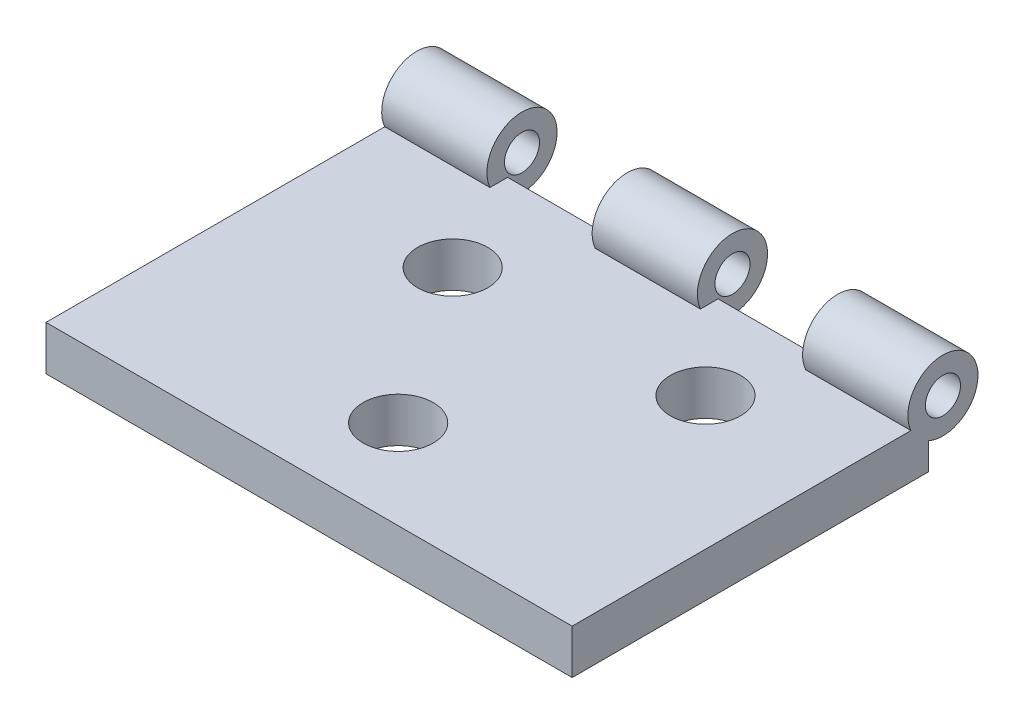
SolidWorks part; units mm, degrees
ref_plane "Front Plane" through (0, 0, 0) normal (0, 0, 1) x (1, 0, 0)
ref_plane "Top Plane" through (0, 0, 0) normal (0, 1, 0) x (1, 0, 0)
ref_plane "Right Plane" through (0, 0, 0) normal (1, 0, 0) x (0, 0, -1)
sketch "Sketch1" plane through (0, 0, 0) normal (0, 1, 0) x (1, 0, 0)
  line L0 (0, 0) -> (-37.5, 0)
  line L1 (-37.5, -25.4) -> (37.5, -25.4)
  line L2 (-37.5, -25.4) -> (-37.5, 25.4)
  line L3 (-37.5, 25.4) -> (37.5, 25.4)
  line L4 (37.5, -25.4) -> (37.5, 25.4)
  line L5 (-37.5, -25.4) -> (37.5, 25.4) construction
  line L6 (-37.5, 25.4) -> (37.5, -25.4) construction
  line L7 (0, 0) -> (37.5, 0)
  line L8 (37.5, 0) -> (18.75, 0)
  line L9 (-37.5, 0) -> (-18.75, 0)
  line L10 (0, 0) -> (0, -25.4)
  line L11 (0, -25.4) -> (0, -12.7)
  circle A0 centre (-15.2792, 10.3491) radius 5
  circle A1 centre (18.5438, 12.5604) radius 5
  circle A2 centre (0, -12.7) radius 5
  point P0 (0, 0)
  dimension "D3" = 10
  dimension "D4" = 10
  dimension "D5" = 10
  dimension "D1" = 75
  dimension "D2" = 50.8
extrude "Boss-Extrude1" add sketch "Sketch1" along normal blind 6.35 contours L0 L7 L4 L3 L2 A1 A0 | A2 L10 L0 L2 L1 L11 | A2 L11 L1 L4 L7 L10 region at (-19.465, 0, 12.7) region at (-0.1467, 0, -12.8119) region at (19.465, 0, 12.7)
sketch "Sketch2" plane through (-37.5, 0, 0) normal (-1, 0, 0) x (0, 0, 1)
  line L0 (-25.4, 6.35) -> (-32.2813, 13.2313)
  circle A0 centre (-27.4485, 8.3985) radius 5
  circle A1 centre (-27.4485, 8.3985) radius 2.5
  point P2 (0, 0)
  point P5 (-27.1968, 8.9074)
  point P6 (0, 0)
  point P7 (-25.9062, 6.8562)
  point P8 (-26.0348, 6.9848)
  point P9 (-27.2657, 8.2157)
  point P10 (-27.4485, 8.3985)
  dimension "D1" = 10
  dimension "D2" = 2.5
extrude "Boss-Extrude2" add sketch "Sketch2" against normal blind 15 contours A0
pattern_linear "LPattern1" count 3 spacing 30 along (1, 0, 0) of "Boss-Extrude2"
extrude "Cut-Extrude2" cut sketch "Sketch2<4>" against normal through all contours A1
sketch "Sketch2<4>" plane through (-37.5, 0, 0) normal (-1, 0, 0) x (0, 0, 1) same geometry as "Sketch2"
sketch "Sketch3" plane through (0, 0, 0) normal (0, 1, 0) x (1, 0, 0)
  line L1 (-37.5, 25.4) -> (37.5, 25.4)
  line L2 (-37.5, 25.4) -> (-37.5, -25.4)
  line L3 (-37.5, -25.4) -> (37.5, -25.4)
  line L4 (37.5, 25.4) -> (37.5, -25.4)
  line L5 (-37.5, 25.4) -> (37.5, -25.4) construction
  line L6 (-37.5, -25.4) -> (37.5, 25.4) construction
  point P0 (0, 0)
